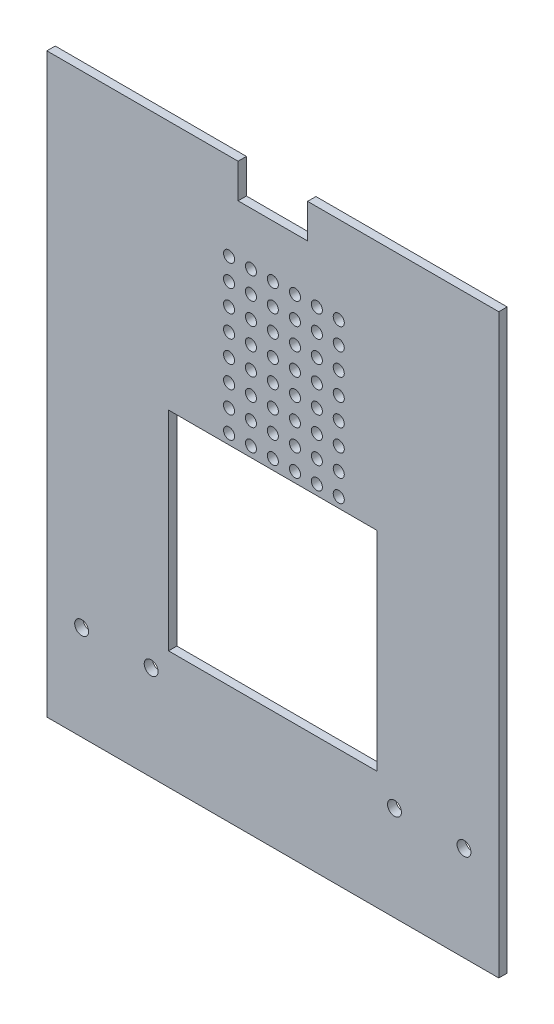
SolidWorks part; units mm, degrees
ref_plane "Front Plane" through (0, 0, 0) normal (0, 0, 1) x (1, 0, 0)
ref_plane "Top Plane" through (0, 0, 0) normal (0, 1, 0) x (1, 0, 0)
ref_plane "Right Plane" through (0, 0, 0) normal (1, 0, 0) x (0, 0, -1)
sketch "Sketch1" plane through (0, 0, 0) normal (0, 0, 1) x (1, 0, 0)
  line L1 (-82.55, 146.05) -> (82.55, 146.05)
  line L2 (-82.55, 146.05) -> (-82.55, -146.05)
  line L3 (-82.55, -146.05) -> (82.55, -146.05)
  line L4 (82.55, 146.05) -> (82.55, -146.05)
  line L5 (-82.55, 146.05) -> (82.55, -146.05) construction
  line L6 (-82.55, -146.05) -> (82.55, 146.05) construction
  point P0 (0, 0)
  dimension "D1" = 165.1
  dimension "D2" = 292.1
extrude "Boss-Extrude1" add sketch "Sketch1" along normal blind 3.048
sketch "Sketch2" plane through (0, 0, 0) normal (0, 0, 1) x (1, 0, 0)
  line L1 (-82.55, -146.05) -> (82.55, -146.05) construction
  line L2 (-82.55, -146.05) -> (82.55, -146.05) construction
  line L3 (8.0869, 109.0549) -> (-8.0869, 109.0549)
  line L4 (8.0869, 109.0549) -> (8.0869, 76.3651)
  line L5 (8.0869, 76.3651) -> (-8.0869, 76.3651)
  line L6 (-8.0869, 109.0549) -> (-8.0869, 76.3651)
  line L7 (8.0869, 109.0549) -> (-8.0869, 76.3651) construction
  line L8 (8.0869, 76.3651) -> (-8.0869, 109.0549) construction
  line L9 (-38.1, -21.59) -> (38.1, -21.59)
  line L10 (-38.1, -21.59) -> (-38.1, -97.79)
  line L11 (-38.1, -97.79) -> (38.1, -97.79)
  line L12 (38.1, -21.59) -> (38.1, -97.79)
  line L13 (-38.1, -21.59) -> (38.1, -97.79) construction
  line L14 (-38.1, -97.79) -> (38.1, -21.59) construction
  circle A1 centre (0, 92.71) radius 10.7315
  circle A2 centre (0, 38.1) radius 2.0193
  circle A3 centre (0, 30.1) radius 2.0193
  circle A4 centre (0, 22.1) radius 2.0193
  circle A5 centre (0, 14.1) radius 2.0193
  circle A6 centre (0, 6.1) radius 2.0193
  circle A7 centre (0, -1.9) radius 2.0193
  circle A8 centre (0, -9.9) radius 2.0193
  circle A9 centre (0, -17.9) radius 2.0193
  circle A10 centre (-8, 38.1) radius 2.0193
  circle A11 centre (-16, 38.1) radius 2.0193
  circle A12 centre (-8, 30.1) radius 2.0193
  circle A13 centre (-16, 30.1) radius 2.0193
  circle A14 centre (-8, 22.1) radius 2.0193
  circle A15 centre (-16, 22.1) radius 2.0193
  circle A16 centre (-8, 14.1) radius 2.0193
  circle A17 centre (-16, 14.1) radius 2.0193
  circle A18 centre (-8, 6.1) radius 2.0193
  circle A19 centre (-16, 6.1) radius 2.0193
  circle A20 centre (-8, -1.9) radius 2.0193
  circle A21 centre (-16, -1.9) radius 2.0193
  circle A22 centre (-8, -9.9) radius 2.0193
  circle A23 centre (-16, -9.9) radius 2.0193
  circle A24 centre (-8, -17.9) radius 2.0193
  circle A25 centre (-16, -17.9) radius 2.0193
  circle A26 centre (24.0869, 14.1) radius 2.0193
  circle A27 centre (8.0869, 14.1) radius 2.0193
  circle A28 centre (8.0869, -17.9) radius 2.0193
  circle A29 centre (24.0869, 6.1) radius 2.0193
  circle A30 centre (16.0869, 6.1) radius 2.0193
  circle A31 centre (8.0869, -1.9) radius 2.0193
  circle A32 centre (8.0869, 30.1) radius 2.0193
  circle A33 centre (24.0869, 22.1) radius 2.0193
  circle A34 centre (24.0869, -1.9) radius 2.0193
  circle A35 centre (24.0869, -9.9) radius 2.0193
  circle A36 centre (8.0869, 6.1) radius 2.0193
  circle A37 centre (16.0869, 22.1) radius 2.0193
  circle A38 centre (8.0869, 22.1) radius 2.0193
  circle A39 centre (8.0869, -9.9) radius 2.0193
  circle A40 centre (24.0869, -17.9) radius 2.0193
  circle A41 centre (16.0869, 14.1) radius 2.0193
  circle A42 centre (16.0869, -17.9) radius 2.0193
  circle A43 centre (16.0869, 30.1) radius 2.0193
  circle A44 centre (24.0869, 30.1) radius 2.0193
  circle A45 centre (16.0869, -9.9) radius 2.0193
  circle A46 centre (16.0869, -1.9) radius 2.0193
  circle A47 centre (16.0869, 38.1) radius 2.0193
  circle A48 centre (8.0869, 38.1) radius 2.0193
  circle A49 centre (24.0869, 38.1) radius 2.0193
  point P2 (0, -59.69)
  dimension "D3" = 21.463
  dimension "D5" = 4.0386
  dimension "D7" = 184.15
  dimension "D2" = 86.36
  dimension "D4" = 152.4
  dimension "D8" = 16.1738
  dimension "D9" = 32.6898
  dimension "D11" = 76.2
  dimension "D12" = 76.2
  dimension "D6" = 3
  dimension "D10" = 8
extrude "Cut-Extrude1" cut sketch "Sketch2" along normal through all contours A13 | A19 | A18 | A20 | A24 | A39 | A31 | L3 L6 L5 L4 | A1 | A3 | A2 | A4 | A5 | A6 | A7 | A8 | A9 | A10 | A12 | A11 | A15 | A14 | A17 | A16 | A21 | A23 | A22 | A25 | L11 L12 L9 L10 | A42 | A40 | A28 | A36 | A27 | A38 | A32 | A48 | A47 | A49 | A43 | A37 | A41 | A30 | A46 | A45 | A35 | A34 | A29 | A26 | A33 | A44 region at (-16, 30.1, 0) region at (-8, 6.1, 0) region at (-16, 6.1, 0) region at (-8, -1.9, 0) region at (-8, -17.9, 0) region at (8.0869, -1.9, 0) region at (8.0869, -9.9, 0)
sketch "Sketch4" plane through (0, 0, 0) normal (0, 0, 1) x (1, 0, 0)
  line L0 (-12.7, 57.3108) -> (-12.7, 69.85)
  line L1 (82.55, 146.05) -> (-82.55, 146.05)
  line L2 (82.55, 146.05) -> (82.55, 69.85)
  line L4 (-82.55, 146.05) -> (-82.55, 69.85)
  line L7 (-12.7, 57.3108) -> (12.7, 57.3108)
  line L9 (12.7, 57.3108) -> (12.7, 69.85)
  line L10 (-82.55, 69.85) -> (-12.7, 69.85)
  line L11 (12.7, 69.85) -> (82.55, 69.85)
  point P5 (0, 146.05)
  dimension "D1" = 165.1
  dimension "D2" = 76.2
  dimension "D3" = 25.4
  dimension "D4" = 69.85
extrude "Cut-Extrude2" cut sketch "Sketch4" along normal through all
sketch "Sketch5" plane through (0, 0, 0) normal (0, 0, -1) x (-1, 0, 0)
  line L0 (82.55, -146.05) -> (-82.55, -146.05) construction
  line L1 (-82.55, -146.05) -> (-82.55, 69.85) construction
  line L2 (0, 1.6764) -> (0, -1.6764) construction
  circle A0 centre (-44.45, -106.299) radius 2.54
  circle A2 centre (-69.85, -106.299) radius 2.54
  circle A3 centre (69.85, -106.299) radius 2.54
  circle A4 centre (44.45, -106.299) radius 2.54
  dimension "D1" = 5.08
  dimension "D2" = 39.751
  dimension "D3" = 25.4
  dimension "D4" = 12.7
extrude "Cut-Extrude3" cut sketch "Sketch5" against normal through all
sketch "Sketch6" plane through (0, 0, 0) normal (0, 0, -1) x (-1, 0, 0)
  line L0 (82.55, 69.85) -> (82.55, -146.05) construction
  line L1 (-82.55, -146.05) -> (82.55, -146.05)
  line L2 (-82.55, -146.05) -> (-82.55, -140.97)
  line L3 (-82.55, -140.97) -> (82.55, -140.97)
  line L4 (82.55, -146.05) -> (82.55, -140.97)
  dimension "D1" = 5.08
extrude "Cut-Extrude4" cut sketch "Sketch6" against normal through all
equation "\"thickness_acrylic0.1\"=0.1in"
equation "\"motor offset\"=6mm"
equation "\"thickness0.25\"=0.225in"
equation "\"thickness0.125\"=0.122in"
